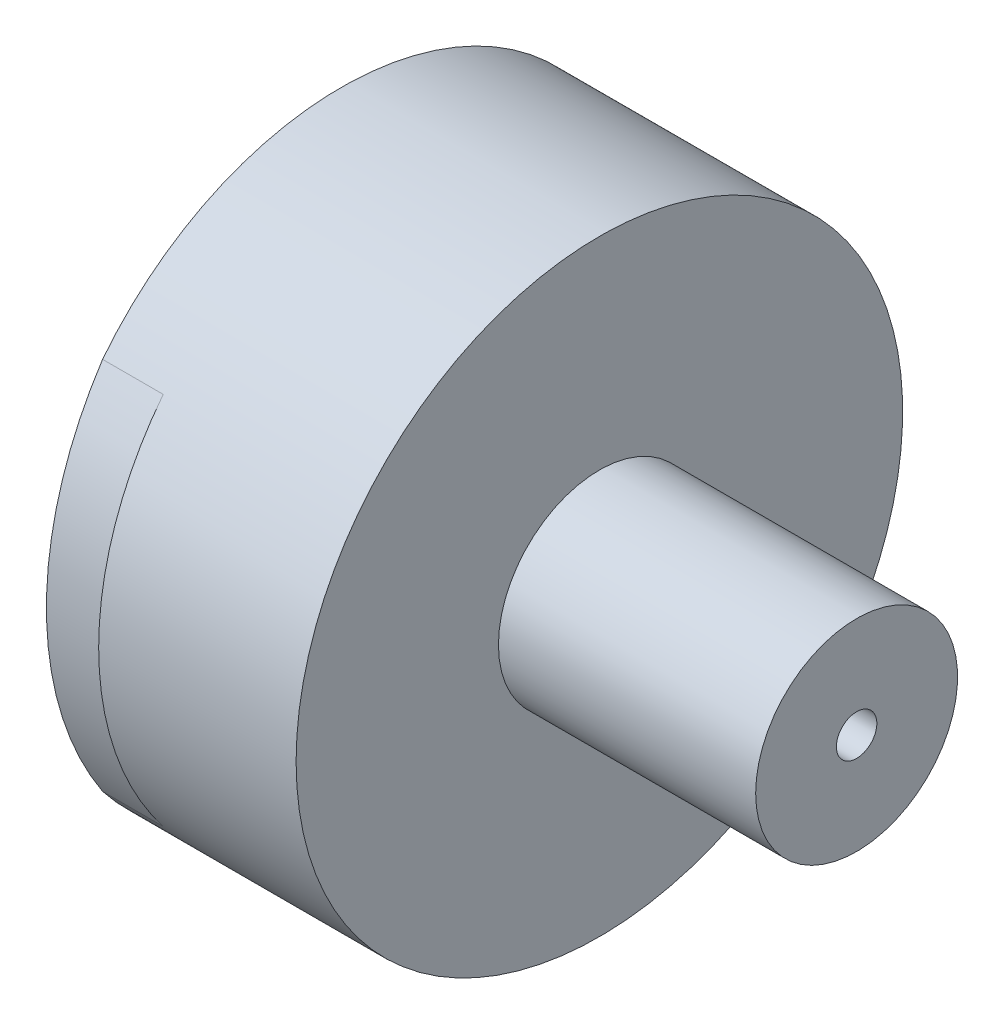
SolidWorks part; units mm, degrees
ref_plane "Front Plane" through (0, 0, 0) normal (0, 0, 1) x (1, 0, 0)
ref_plane "Top Plane" through (0, 0, 0) normal (0, 1, 0) x (1, 0, 0)
ref_plane "Right Plane" through (0, 0, 0) normal (1, 0, 0) x (0, 0, -1)
sketch "CircularBase" plane through (0, 0, 0) normal (0, 0, 1) x (1, 0, 0)
  line L0 (-5.0594, 0) -> (7.0797, 0) construction
  line L1 (0, 0) -> (0, 0.5)
  line L2 (0, 0.5) -> (-2, 0.5)
  line L3 (-2, 0.5) -> (-2, 2)
  line L4 (-2, 2) -> (-1.25, 2)
  line L5 (-1.25, 2) -> (-1.25, 1.5)
  line L6 (-1.25, 1.5) -> (5.15, 1.5)
  line L7 (5.15, 1.5) -> (5.15, 2.5)
  line L8 (5.15, 2.5) -> (5.9, 2.5)
  line L9 (5.9, 2.5) -> (5.9, 0)
  line L11 (0, 0) -> (5.9, 0)
  line L12 (7.0797, 0) -> (14.1483, 0) construction
  dimension "D1" = 0.75
  dimension "D2" = 0.75
  dimension "D3" = 1
  dimension "D4" = 0.5
  dimension "D5" = 1.5
  dimension "D6" = 0.5
  dimension "D7" = 2.5
  dimension "D8" = 2
  dimension "D9" = 5.9
revolve "CircularBaseRevolve" add sketch "CircularBase" angle 360 about L12
ref_plane "BasePlane" through (-2, 0, 0) normal (-1, 0, 0) x (0, 0, 1)
sketch "NotchCutSketc" plane through (-2, 0, 0) normal (-1, 0, 0) x (0, 0, 1)
  line L0 (0, 2) -> (0, -2) construction
  line L1 (-0.5, 0) -> (-0.5, 1.9365)
  line L2 (-0.5, 1.9365) -> (0.5, 1.9365)
  line L3 (-0.5, 0) -> (-0.5, -1.9365)
  line L4 (-0.5, -1.9365) -> (0.5, -1.9365)
  line L5 (0.5, 0) -> (0.5, -1.9365)
  line L6 (0.5, 0) -> (0.5, 1.9365)
  circle A0 centre (0, 0) radius 2 construction
  circle A1 centre (0, 0) radius 0.5 construction
  circle A2 centre (0, 0) radius 0.5 construction
  point P15 (0, -1.9365)
  point P17 (0, 1.9365)
extrude "NotchCut" cut sketch "NotchCutSketc" against normal blind 3
fillet "InsideNotchFillet1" radius 0.4 1 edges at (1, 0, -0.5) type face fillet first side face at (-0.875, 0, -0.5) second side face at (1, 0, 0)
fillet "InsideNotchFillet2" radius 0.4 1 edges at (1, 0, 0.5) type face fillet first side face at (-0.875, 0, 0.5) second side face at (1, 0, 0.2021)
fillet "OutsideNotchFillet" radius 0.1 16 edges at (-2, 0, 0.5) (-2, 0, -0.5) (-0.325, -1.4142, -0.5) (0.915, -1.4594, -0.3465) (1, -1.5, 0) (0.8413, -1.4403, 0.419) (-0.325, 1.4142, 0.5) (0.915, 1.4594, 0.3465) (1, 1.5, 0) (0.8413, 1.4403, -0.419) (-1.625, 1.9365, 0.5) (-1.625, 1.9365, -0.5) (-1.625, -1.9365, -0.5) (-0.325, -1.4142, 0.5) (-0.325, 1.4142, -0.5) (-1.25, -1.6754, 0.5)
ref_plane "TopBasePlane" through (5.9, 0, 0) normal (1, 0, 0) x (0, 0, -1)
sketch "TopCircularBaseExtrudeSketch" plane through (5.9, 0, 0) normal (1, 0, 0) x (0, 0, -1)
  line L0 (0, 2.007) -> (0, -2.007) construction
  line L13 (-2.0033, 0) -> (2.0033, 0) construction
  line L16 (-2.0033, -0.7505) -> (-2.0033, 0.7505)
  line L17 (-2.0033, 0.7505) -> (-0.7468, 0.7505)
  line L18 (0.7468, 2.007) -> (-0.7468, 2.007)
  line L19 (-0.7468, 2.007) -> (-0.7468, 0.7505)
  line L20 (2.0033, -0.7505) -> (2.0033, 0.7505)
  line L21 (2.0033, 0.7505) -> (0.7468, 0.7505)
  line L22 (0.7468, 2.007) -> (0.7468, 0.7505)
  line L23 (2.0033, -0.7505) -> (0.7468, -0.7505)
  line L24 (0.7468, -2.007) -> (0.7468, -0.7505)
  line L25 (-2.0033, -0.7505) -> (-0.7468, -0.7505)
  line L26 (-0.7468, -2.007) -> (-0.7468, -0.7505)
  line L27 (0.7468, -2.007) -> (-0.7468, -2.007)
  point P16 (2.0033, 0)
extrude "TopCircularBaseExtrude" add sketch "TopCircularBaseExtrudeSketch" along normal blind 7.9
fillet "TopCircularBaseFillet" radius 0.4 12 edges at (13.8, 1.3788, 0.7468) (13.8, 1.3788, -0.7468) (13.8, 0.7505, 1.375) (13.8, 0.7505, -1.375) (13.8, 0, -2.0033) (13.8, -0.7505, -1.375) (13.8, -1.3788, -0.7468) (13.8, -2.007, 0) (13.8, 0, 2.0033) (13.8, 2.007, 0) (13.8, -0.7505, 1.375) (13.8, -1.3788, 0.7468)
fillet "TopCircularbaseSideFillet" radius 0.1 36 edges at (5.9, 1.3788, 0.7468) (5.9, -2.007, 0) (5.9, -0.7505, -1.375) (5.9, 0.7505, -1.375) (5.9, 2.007, 0) (5.9, 0.7505, 1.375) (5.9, -0.7505, 1.375) (13.6828, -1.8899, -0.6296) (13.6828, -0.6334, -0.6296) (13.6828, -0.6334, 0.6296) (13.6828, -1.8899, 0.6296) (13.6828, -0.6334, -1.8861) (13.6828, 0.6334, -1.8861) (13.6828, 0.6334, -0.6296) (13.6828, 1.8899, -0.6296) (13.6828, 0.6334, 1.8861) (13.6828, 0.6334, 0.6296) (13.6828, 1.8899, 0.6296) (13.6828, -0.6334, 1.8861) (5.9, -1.3788, -0.7468) (9.65, -2.007, -0.7468) (9.65, -0.7505, -0.7468) (5.9, -1.3788, 0.7468) (9.65, -0.7505, 0.7468) (9.65, -2.007, 0.7468) (5.9, 0, -2.0033) (9.65, -0.7505, -2.0033) (9.65, 0.7505, -2.0033) (5.9, 1.3788, -0.7468) (9.65, 0.7505, -0.7468) (9.65, 2.007, -0.7468) (5.9, 0, 2.0033) (9.65, 0.7505, 2.0033) (9.65, 0.7505, 0.7468) (9.65, 2.007, 0.7468) (9.65, -0.7505, 2.0033)
ref_plane "Plane1" [suppressed] through (0, -2.007, 0) normal (0, -1, 0) x (-1, 0, 0)
sketch "CircularTipSketch" [suppressed] plane through (0, -2.007, 0) normal (0, -1, 0) x (-1, 0, 0)
  line L0 (-6, 2.0033) -> (-6, -2.0033)
  line L1 (-6, -2.0033) -> (-6, -2.5355)
  line L2 (-6, -2.5355) -> (2.115, -2.5355)
  line L3 (2.115, -2.5355) -> (1.9623, 2.8509)
  line L4 (1.9623, 2.8509) -> (-6, 2.7898)
  line L5 (-6, 2.7898) -> (-6, 2.0033)
extrude "CircularTip" [suppressed] cut sketch "CircularTipSketch" against normal through all
ref_plane "Plane2" [suppressed] through (6, 0, 0) normal (-1, 0, 0) x (0, 0, 1)
mirror "Mirror2" [suppressed]
ref_plane "Plane3" through (0, 2.007, 0) normal (0, 1, 0) x (1, 0, 0)
sketch "BaseCutSketch" plane through (0, 2.007, 0) normal (0, 1, 0) x (1, 0, 0)
  line L0 (5.15, 2.5558) -> (5.15, -2.5)
  line L1 (5.15, -2.5) -> (-2.0426, -2.5)
  line L2 (-2.0426, -2.5) -> (-2.0426, 2.5558)
  line L3 (-2.0426, 2.5558) -> (5.15, 2.5558)
extrude "BaseCut" cut sketch "BaseCutSketch" against normal through all contours L3 L2 L1 L0 region at (1.5537, 2.007, -0.0279)
ref_plane "Plane4" through (13.8, 0, 0) normal (1, 0, 0) x (0, 0, -1)
sketch "NotchCutSketch" plane through (0, 0, 0) normal (0, 1, 0) x (1, 0, 0)
  line L7 (7.7505, 3.747) -> (7.7505, 0)
  line L14 (7.7505, 0) -> (10.818, 0) construction
  line L19 (7.7505, 0) -> (5.15, 0)
  line L20 (5.15, 2.5) -> (5.15, -2.5) construction
  line L21 (5.15, 0) -> (5.15, 4)
  line L22 (5.15, 4) -> (6.4505, 4)
  line L23 (6.4505, 4) -> (6.4505, 3.747)
  line L24 (6.4505, 3.747) -> (7.7505, 3.747)
  point P16 (7.1, 2.25)
  dimension "D1" = 1.3
  dimension "D2" = 4
revolve "CircularEvolveWithNotch" [suppressed] add sketch "NotchCutSketch" angle 360 about L14
ref_plane "Plane5" through (5.15, 0, 0) normal (-1, 0, 0) x (0, 0, 1)
sketch "CrossHoleCutSketch" plane through (5.15, 0, 0) normal (-1, 0, 0) x (0, 0, 1)
  line L0 (-0.8429, 0.8584) -> (-0.8429, 1.9149)
  line L1 (-0.6429, 2.1149) -> (0.6506, 2.1149)
  line L2 (0.8506, 1.9149) -> (0.8506, 0.8584)
  line L3 (0.8506, 0.8584) -> (1.9071, 0.8584)
  line L4 (-1.8994, 0.8584) -> (-0.8429, 0.8584)
  line L5 (-0.8429, -0.8427) -> (-1.8994, -0.8427)
  line L6 (-0.8429, -0.8427) -> (-0.8429, -1.8992)
  line L7 (-0.6429, -2.0992) -> (0.6506, -2.0992)
  line L8 (0.8506, -1.8992) -> (0.8506, -0.8427)
  line L9 (0.8506, -0.8427) -> (1.9071, -0.8427)
  line L10 (2.1071, -0.6427) -> (2.1071, 0.6584)
  line L11 (-2.0994, -0.6427) -> (-2.0994, 0.6584)
  arc A0 (-0.8429, 1.9149) -> (-0.6429, 2.1149) centre (-0.6429, 1.9149) cw
  arc A1 (0.8506, 1.9149) -> (0.6506, 2.1149) centre (0.6506, 1.9149) ccw
  arc A2 (1.9071, 0.8584) -> (2.1071, 0.6584) centre (1.9071, 0.6584) cw
  arc A3 (1.9071, -0.8427) -> (2.1071, -0.6427) centre (1.9071, -0.6427) ccw
  arc A4 (0.8506, -1.8992) -> (0.6506, -2.0992) centre (0.6506, -1.8992) cw
  arc A5 (-0.6429, -2.0992) -> (-0.8429, -1.8992) centre (-0.6429, -1.8992) cw
  arc A6 (-1.8994, -0.8427) -> (-2.0994, -0.6427) centre (-1.8994, -0.6427) cw
  arc A7 (-1.8994, 0.8584) -> (-2.0994, 0.6584) centre (-1.8994, 0.6584) ccw
extrude "CrossHoleCut" [suppressed] cut sketch "CrossHoleCutSketch" against normal through all
ref_plane "Plane11" [suppressed] through (7.7505, 0, 0) normal (1, 0, 0) x (0, 0, -1)
sketch "Sketch16" [suppressed] plane through (7.7505, 0, 0) normal (1, 0, 0) x (0, 0, -1)
  line L1 (0.8429, 0.8584) -> (0.8429, 1.9149)
  line L3 (-0.8506, 0.8584) -> (-1.9071, 0.8584)
  line L4 (-2.1071, 0.6584) -> (-2.1071, -0.6427)
  line L5 (-1.9071, -0.8427) -> (-0.8506, -0.8427)
  line L6 (-0.8506, -0.8427) -> (-0.8506, -1.8992)
  line L7 (0.8429, -1.8992) -> (0.8429, -0.8427)
  line L8 (0.8429, -0.8427) -> (1.8994, -0.8427)
  line L9 (2.0994, -0.6427) -> (2.0994, 0.7075)
  line L10 (0.8429, 0.8584) -> (1.8994, 0.8584)
  line L11 (-0.6506, -2.0992) -> (0.6429, -2.0992)
  line L12 (-0.8506, 0.8584) -> (-0.8506, 1.9149)
  line L13 (-0.6506, 2.1149) -> (0.6429, 2.1149)
  circle A0 centre (0, 0) radius 4
  arc A1 (-1.9071, -0.8427) -> (-2.1071, -0.6427) centre (-1.9071, -0.6427) cw
  arc A2 (-2.1071, 0.6584) -> (-1.9071, 0.8584) centre (-1.9071, 0.6584) cw
  arc A6 (1.8994, 0.8584) -> (2.0994, 0.7075) centre (1.8994, 0.6504) cw
  arc A7 (2.0994, -0.6427) -> (1.8994, -0.8427) centre (1.8994, -0.6427) cw
  arc A8 (0.8429, -1.8992) -> (0.6429, -2.0992) centre (0.6429, -1.8992) cw
  arc A9 (-0.8506, -1.8992) -> (-0.6506, -2.0992) centre (-0.6506, -1.8992) ccw
  arc A10 (-0.8506, 1.9149) -> (-0.6506, 2.1149) centre (-0.6506, 1.9149) cw
  arc A11 (0.8429, 1.9149) -> (0.6429, 2.1149) centre (0.6429, 1.9149) ccw
extrude "CircularCrossHolwCircle" [suppressed] add sketch "Sketch16" along normal blind 1.25
fillet "EdgesFillet" [suppressed] radius 0.1
fillet "Fillet2" [suppressed] radius 0.1
ref_plane "Plane6" through (0, 0, -2.0033) normal (0, 0, -1) x (-1, 0, 0)
sketch "Sketch1" plane through (0, 0, -2.0033) normal (0, 0, -1) x (-1, 0, 0)
  line L0 (-5.9, 2.5) -> (-5.9, -2.5)
  line L1 (-5.9, 2.5) -> (-5.9, -2.5) construction
  line L2 (-5.9, -2.5) -> (-13.8486, -2.5)
  line L3 (-13.8486, -2.5) -> (-13.8486, 2.5)
  line L4 (-13.8486, 2.5) -> (-5.9, 2.5)
extrude "RemovedMaterial" cut sketch "Sketch1" against normal through all
sketch "Sketch2" plane through (0, 0, -2.0033) normal (0, 0, -1) x (-1, 0, 0)
  line L1 (-11.5273, 0) -> (-12.3621, 0) construction
  line L2 (-5.15, 3.75) -> (-5.15, 0.25)
  line L3 (-5.15, 3.75) -> (-8.341, 3.75)
  line L4 (-8.341, 1.2482) -> (-11.5214, 1.2482)
  line L6 (-11.5214, 1.2482) -> (-11.5214, 0.25)
  line L8 (-8.341, 3.75) -> (-8.341, 1.2482)
  line L10 (-5.15, -2.5) -> (-5.15, 2.5) construction
  line L11 (-5.15, 0.25) -> (-11.5214, 0.25)
  dimension "D1" = 3.5
revolve "Revolve2" add sketch "Sketch2" angle 360 about L1
ref_plane "Plane8" through (5.9, 0, 0) normal (1, 0, 0) x (0, 0, -1)
sketch "Sketch13" plane through (5.9, 0, 0) normal (1, 0, 0) x (0, 0, -1)
  arc A0 (-0.9483, 2.3132) -> (-0.9483, -2.3132) centre (0, 0) ccw
  arc A2 (-0.9483, 2.3132) -> (-0.9483, -2.3132) centre (2.5573, 0) ccw
  dimension "D1" = 2.5
extrude "RemovedMaterial2" cut sketch "Sketch13" against normal through all
sketch "Sketch14" plane through (5.9, 0, 0) normal (1, 0, 0) x (0, 0, -1)
  line L0 (2.0033, -0.25) -> (2.0033, 0.25) construction
  circle A0 centre (2.0033, 0) radius 0.2516
ref_plane "ShellPlane" through (5.15, 0, 0) normal (-1, 0, 0) x (0, 0, 1)
sketch "ShellSketch" plane through (5.15, 0, 0) normal (-1, 0, 0) x (0, 0, 1)
  circle A0 centre (-2.0033, 0) radius 2.45
  dimension "D1" = 4.9
extrude "ShellFeature" cut sketch "ShellSketch" against normal blind 1.6
ref_plane "Plane13" [suppressed] through (8.341, 0, 0) normal (1, 0, 0) x (0, 0, -1)
sketch "RemoveMaterialSketch3" [suppressed] plane through (8.341, 0, 0) normal (1, 0, 0) x (0, 0, -1)
  circle A0 centre (2.0033, 0) radius 1.2482
extrude "RemoveMaterial3" [suppressed] cut sketch "RemoveMaterialSketch3" along normal through all
sketch "Sketch21" [suppressed] plane through (8.341, 0, 0) normal (1, 0, 0) x (0, 0, -1)
  circle A0 centre (2.0033, 0) radius 2.4
  circle A1 centre (2.0033, 0) radius 2
  dimension "D1" = 4.8
  dimension "D2" = 4
extrude "CylindereExtrudeVertical" [suppressed] add sketch "Sketch21" along normal blind 2
sketch "ThroughHoleSketch" [suppressed] plane through (8.341, 0, 0) normal (1, 0, 0) x (0, 0, -1)
  circle A0 centre (2.0033, 0) radius 2
extrude "ThroughHole" [suppressed] cut sketch "ThroughHoleSketch" against normal through all
ref_plane "Plane14" [suppressed] through (5.15, 0, 0) normal (-1, 0, 0) x (0, 0, 1)
sketch "Sketch23" [suppressed] plane through (5.15, 0, 0) normal (-1, 0, 0) x (0, 0, 1)
  circle A0 centre (-2.0033, 0) radius 2.4
  dimension "D1" = 4.8
extrude "Cut-Extrude6" [suppressed] cut sketch "Sketch23" against normal blind 1.6
ref_plane "BisectingPlane" [suppressed] through (6.7455, 0, 0) normal (1, 0, 0) x (0, 0, -1)
sketch "Sketch24" [suppressed] plane through (6.7455, 0, 0) normal (1, 0, 0) x (0, 0, -1)
  line L0 (2.0033, 0) -> (2.0033, 3.4935) construction
  line L2 (3.5835, 3.5518) -> (3.5835, 8.4935)
  line L4 (2.0033, 9.1481) -> (2.0033, 10.1942) construction
  line L5 (2.0033, 9.1481) -> (2.0033, 3.5518)
  line L6 (2.0033, 3.5518) -> (3.5835, 3.5518)
  arc A0 (2.0033, 9.1481) -> (3.5835, 8.4935) centre (2.0033, 6.9132) cw
  point P7 (2.0033, 3.4935)
revolve "CylinderRevolve" [suppressed] add sketch "Sketch24" angle 360 about L4
sketch "Sketch25" [suppressed] plane through (6.7455, 0, 0) normal (1, 0, 0) x (0, 0, -1)
  line L0 (2.0033, 4.2) -> (2.0033, 10.2085) construction
  line L1 (3.5835, 8.4935) -> (0.423, 8.4935) construction
  arc A0 (3.5835, 3.8914) -> (0.423, 3.8914) centre (2.0033, 0) ccw construction
  circle A1 centre (2.0033, 8.4935) radius 1.5349
extrude "Boss-Extrude3" [suppressed] add sketch "Sketch25" against normal blind 7
sketch "Sketch27" [suppressed] plane through (6.7455, 0, 0) normal (1, 0, 0) x (0, 0, -1)
  line L0 (2.0033, 8.4935) -> (2.0033, 10.0284)
  line L1 (3.5835, 8.4935) -> (0.423, 8.4935) construction
  line L2 (2.0033, 8.4935) -> (0.423, 8.4935)
  line L3 (2.0033, 10.379) -> (2.0033, 10.0284) construction
  arc A0 (3.5376, 8.5382) -> (0.469, 8.5382) centre (2.0033, 8.4935) ccw construction
  arc A1 (0.423, 8.4935) -> (2.0033, 10.0284) centre (1.9586, 8.4935) cw
revolve "Revolve4" [suppressed] add sketch "Sketch27" angle 360 about L3
ref_plane "Plane17" [suppressed] through (-0.2545, 0, 0) normal (-1, 0, 0) x (0, 0, 1)
sketch "Sketch28" [suppressed] plane through (-0.2545, 0, 0) normal (-1, 0, 0) x (0, 0, 1)
  line L0 (-2.0033, 10.0284) -> (-2.0033, 6.9586) construction
  line L1 (-3.5382, 8.4935) -> (-0.4683, 8.4935) construction
  arc A0 (-3.5382, 8.4935) -> (-0.4683, 8.4935) centre (-2.0033, 8.4935) ccw construction
  circle A1 centre (-2.0033, 8.4935) radius 0.5026
extrude "SmallHoleInCylinder" [suppressed] cut sketch "Sketch28" against normal blind 3
ref_plane "Plane18" [suppressed] through (21.6, 0, 0) normal (1, 0, 0) x (0, 0, -1)
sketch "Sketch29" [suppressed] plane through (21.6, 0, 0) normal (1, 0, 0) x (0, 0, -1)
  line L7 (0.776, -2.675) -> (-1.1035, -2.675) construction
  line L8 (1.0733, 2.6336) -> (1.0733, 1.1385) construction
  line L9 (-1.0733, 2.6336) -> (-1.0733, 1.1201) construction
  line L10 (-1.0733, 2.6336) -> (1.0733, 2.652)
  line L11 (1.0733, 2.652) -> (1.0733, 1.1385)
  line L12 (1.0733, 1.1385) -> (2.4478, 1.1385)
  line L13 (2.4478, 1.1385) -> (2.4478, -1.1615)
  line L14 (2.4478, -1.1615) -> (1.0733, -1.1615)
  line L16 (1.0733, -2.675) -> (-1.1035, -2.675)
  line L17 (-1.1035, -2.675) -> (-1.1035, -1.1615)
  line L18 (-1.1035, -1.1615) -> (-2.4478, -1.1615)
  line L19 (-2.4478, -1.1615) -> (-2.4478, 1.1201)
  line L20 (-2.4478, 1.1201) -> (-1.0733, 1.1201)
  line L21 (-1.0733, 1.1201) -> (-1.0733, 2.6336)
  line L23 (1.0733, -1.1615) -> (1.0733, -2.675)
  circle A0 centre (0, 0) radius 3.45
  dimension "D1" = 6.9
  dimension "D3" = 0.775
  dimension "D2" = 2.3
extrude "Boss-Extrude5" [suppressed] add sketch "Sketch29" along normal blind 15.8 separate body
ref_plane "Plane19" [suppressed] through (0, 0, -2.0033) normal (0, 0, -1) x (-1, 0, 0)
sketch "Sketch30" [suppressed] plane through (0, 0, -2.0033) normal (0, 0, -1) x (-1, 0, 0)
  line L0 (-21.6, 3.4921) -> (-21.6, -3.45)
  line L1 (-21.6, 3.1156) -> (-21.6, -3.1156) construction
  line L2 (-21.6, -3.45) -> (-21.6, 3.45) construction
  line L3 (-21.6, -3.45) -> (9.8373, -3.45)
  line L4 (9.8373, -3.45) -> (9.8373, 3.4921)
  line L5 (9.8373, 3.4921) -> (-21.6, 3.4921)
extrude "Cut-Extrude7" [suppressed] cut sketch "Sketch30" against normal through all
sketch "Sketch31" [suppressed] plane through (21.6, 0, 0) normal (1, 0, 0) x (0, 0, -1)
  line L0 (0, -3.485) -> (0, 0) construction
  line L1 (0, 0) -> (2.3068, 0) construction
  line L3 (-2.6444, 2.1051) -> (-2.7334, 2.1051)
  line L5 (-2.6444, -2.1051) -> (-2.7334, -2.1051)
  line L7 (2.6444, -2.1051) -> (2.7334, -2.1051)
  line L8 (2.6444, 2.1051) -> (2.7334, 2.1051)
  circle A0 centre (0, 0) radius 3.45 construction
  arc A1 (-2.7334, 2.1051) -> (-1.8163, 2.9332) centre (-0.5362, 0.5938) cw
  arc A2 (-2.7334, -2.1051) -> (-1.8163, -2.9332) centre (-0.5362, -0.5938) ccw
  arc A3 (2.7334, -2.1051) -> (1.8163, -2.9332) centre (0.5362, -0.5938) cw
  arc A4 (2.7334, 2.1051) -> (1.8163, 2.9332) centre (0.5362, 0.5938) ccw
  arc A5 (-2.6444, 2.1051) -> (-1.8163, 2.9332) centre (-2.6889, 2.9777) ccw
  arc A6 (2.6444, 2.1051) -> (1.8163, 2.9332) centre (2.6889, 2.9777) cw
  arc A7 (-2.6444, -2.1051) -> (-1.8163, -2.9332) centre (-2.6889, -2.9777) cw
  arc A8 (2.6444, -2.1051) -> (1.8163, -2.9332) centre (2.6889, -2.9777) ccw
extrude "Cut-Extrude8" [suppressed] cut sketch "Sketch31" along normal through all
fillet "Fillet3" [suppressed] radius 0.4
